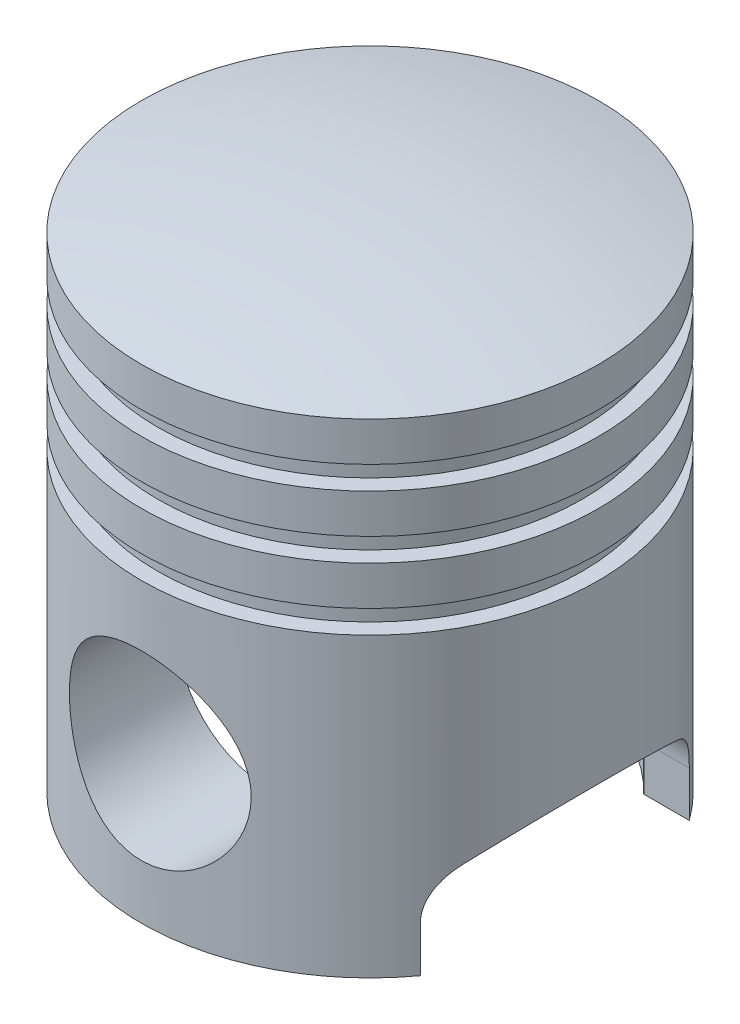
SolidWorks part; units mm, degrees
ref_plane "Plano frontal" through (0, 0, 0) normal (0, 0, 1) x (1, 0, 0)
ref_plane "Plano superior" through (0, 0, 0) normal (0, 1, 0) x (1, 0, 0)
ref_plane "Plano direito" through (0, 0, 0) normal (1, 0, 0) x (0, 0, -1)
sketch "Esboço26" plane through (0, 0, 0) normal (0, 1, 0) x (1, 0, 0)
  circle A0 centre (0, 0) radius 42.5
  dimension "D1" = 85
extrude "Ressalto-extrusão4" add sketch "Esboço26" along normal blind 90
sketch "Esboço27" plane through (0, 90, 0) normal (0, 1, 0) x (1, 0, 0)
  circle A0 centre (0, 0) radius 39.5
  dimension "D1" = 79
extrude "Corte-extrusão15" cut sketch "Esboço27" against normal blind 4.3 from offset 7.3 flip side to cut offset against normal yes
pattern_linear "Padrão linear2" count 3 spacing 11.6 along (0, -1, 0) of "Corte-extrusão15"
sketch "Esboço28" plane through (0, 0, 0) normal (0, -1, 0) x (1, 0, 0)
  circle A0 centre (0, 0) radius 36
  dimension "D1" = 72
extrude "Corte-extrusão16" cut sketch "Esboço28" against normal blind 85
dome "Domo1" faces to dome 1 distance 5 reverse direction no elliptical dome no face at (0, 90, 42.5) parameters "D1"=5
sketch "Esboço29" plane through (0, 0, 0) normal (0, 0, 1) x (1, 0, 0)
  line L0 (-42.5, 0) -> (42.5, 0) construction
  circle A0 centre (0, 27) radius 16.9
  dimension "D1" = 33.8
  dimension "D2" = 27
extrude "Corte-extrusão18" cut sketch "Esboço29" against normal mid plane 85
sketch "Esboço30" plane through (0, 0, 0) normal (1, 0, 0) x (0, 0, -1)
  line L0 (0, 116.4822) -> (0, -24.5255) construction
  line L1 (-25, 0) -> (-25, 13.7)
  line L2 (-42.5, 0) -> (42.5, 0) construction
  line L3 (25, 0) -> (25, 13.7)
  line L4 (-25, 0) -> (25, 0)
  arc A0 (-25, 13.7) -> (25, 13.7) centre (0, -17.525) cw
  dimension "D3" = 40
  dimension "D1" = 13.7
  dimension "D2" = 50
extrude "Corte-extrusão19" cut sketch "Esboço30" against normal mid plane 85
fillet "Filete1" radius 10 4 edges at (30.1365, 13.7, -25) (30.1365, 13.7, 25) (-30.1365, 13.7, -25) (-30.1365, 13.7, 25)
sketch "Esboço31" plane through (0, 0, 0) normal (0, 0, 1) x (1, 0, 0)
  circle A0 centre (0, 27) radius 16.9 construction
  circle A1 centre (0, 27) radius 16.9
  circle A2 centre (0, 27) radius 22.5
  dimension "D1" = 45
extrude "Ressalto-extrusão5" add sketch "Esboço31" along normal up to next from offset 19
mirror "Espelhar1" about plane through (0, 0, 0) normal (0, 0, 1) of "Ressalto-extrusão5"
